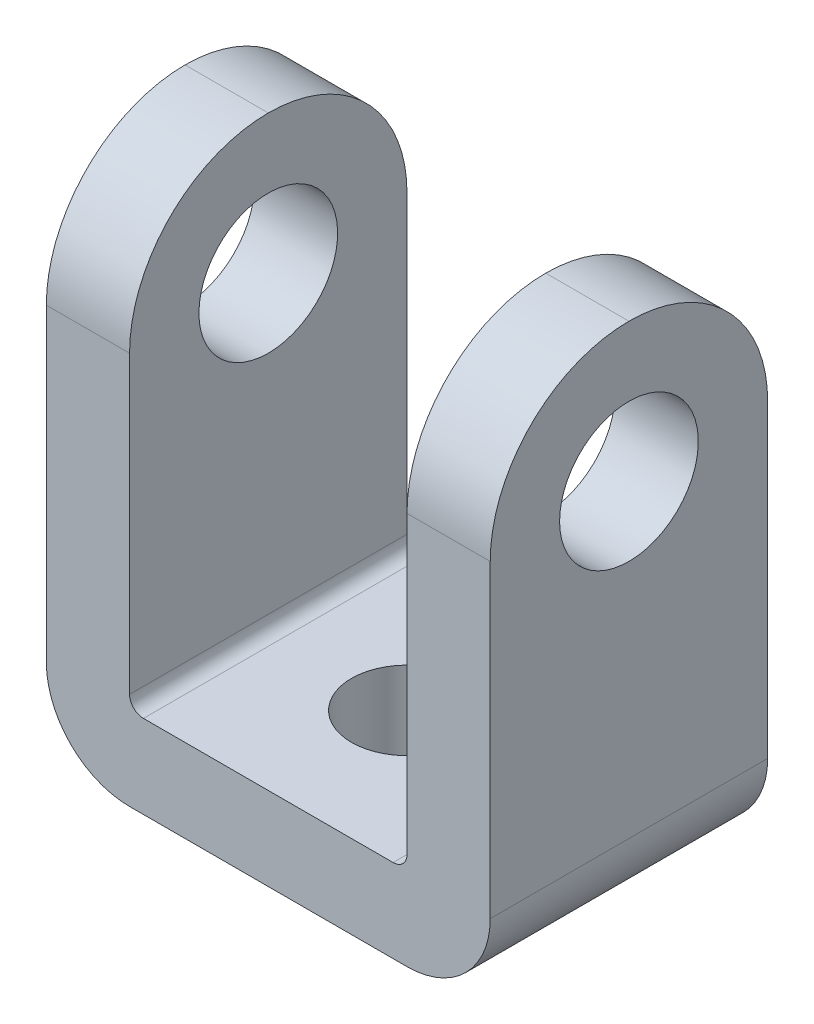
SolidWorks part; units mm, degrees
ref_plane "Front Plane" through (0, 0, 0) normal (0, 0, 1) x (1, 0, 0)
ref_plane "Top Plane" through (0, 0, 0) normal (0, 1, 0) x (1, 0, 0)
ref_plane "Right Plane" through (0, 0, 0) normal (1, 0, 0) x (0, 0, -1)
sketch "Sketch1" plane through (0, 0, 0) normal (0, 0, 1) x (1, 0, 0)
  line L0 (13, 0) -> (16, 0)
  line L1 (0, 0) -> (3, 0)
  line L2 (0, 0) -> (0, -19.1484)
  line L3 (0, -19.1484) -> (16, -19.1484)
  line L4 (16, 0) -> (16, -19.1484)
  line L6 (3, 0) -> (3, -16.1484)
  line L7 (3, -16.1484) -> (13, -16.1484)
  line L8 (13, 0) -> (13, -16.1484)
  dimension "D1" = 3
  dimension "D2" = 3
  dimension "D3" = 10
  dimension "D4" = 3
extrude "Boss-Extrude1" add sketch "Sketch1" along normal blind 10
sketch "Sketch2" plane through (0, 0, 0) normal (-1, 0, 0) x (0, 0, 1)
  line L0 (10, 0) -> (0, 0) construction
  line L1 (0, 0) -> (0, -19.1484) construction
  circle A0 centre (5, -5) radius 2.5
  dimension "D3" = 5
  dimension "D1" = 5
  dimension "D2" = 5
extrude "Cut-Extrude1" cut sketch "Sketch2" against normal through all
sketch "Sketch3" plane through (0, -16.1484, 0) normal (0, 1, 0) x (1, 0, 0)
  line L0 (13, 0) -> (3, 0) construction
  line L1 (3, -10) -> (3, 0) construction
  circle A0 centre (8, -5) radius 2
  dimension "D3" = 4
  dimension "D1" = 5
  dimension "D2" = 5
extrude "Cut-Extrude2" cut sketch "Sketch3" against normal up to next
fillet "Fillet1" radius 5 4 edges at (14.5, 0, 10) (14.5, 0, 0) (1.5, 0, 0) (1.5, 0, 10)
fillet "Fillet2" radius 3 2 edges at (16, -19.1484, 5) (0, -19.1484, 5)
fillet "Fillet3" radius 0.5 2 edges at (13, -16.1484, 5) (3, -16.1484, 5)
